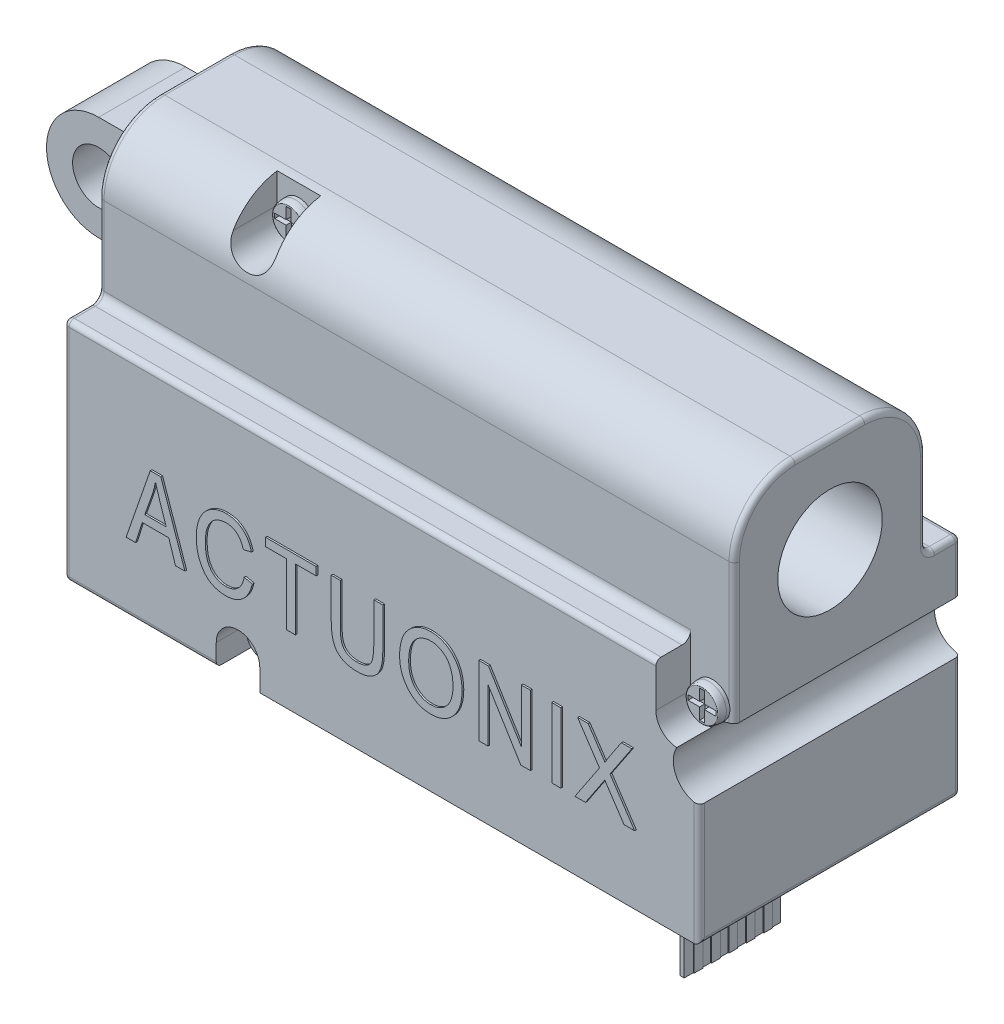
SolidWorks part; units mm, degrees
other "Body"
other "ConnectingWires"
other "Screw2"
other "Screw3"
other "Screw1"
ref_plane "Front Plane" through (0, 0, 0) normal (0, 0, 1) x (1, 0, 0)
ref_plane "Top Plane" through (0, 0, 0) normal (0, 1, 0) x (1, 0, 0)
ref_plane "Right Plane" through (0, 0, 0) normal (1, 0, 0) x (0, 0, -1)
sketch "Sketch1" plane through (0, 0, 0) normal (0, 0, 1) x (1, 0, 0)
  line L1 (-18.25, 10.75) -> (18.25, 10.75)
  line L2 (-18.25, 10.75) -> (-18.25, -10.75)
  line L3 (-18.25, -10.75) -> (18.25, -10.75)
  line L4 (18.25, 10.75) -> (18.25, -10.75)
  line L5 (-18.25, 10.75) -> (18.25, -10.75) construction
  line L6 (-18.25, -10.75) -> (18.25, 10.75) construction
  point P0 (0, 0)
  dimension "D1" = 36.5
  dimension "D2" = 21.5
extrude "Boss-Extrude1" add sketch "Sketch1" along normal mid plane 15
sketch "Sketch2" plane through (18.25, 0, 0) normal (1, 0, 0) x (0, 0, -1)
  line L0 (-7.5, -10.75) -> (-7.5, 2.25)
  line L1 (-7.5, -10.75) -> (-7.5, 10.75) construction
  line L2 (7.5, 2.25) -> (7.5, -10.75)
  line L3 (7.5, -10.75) -> (7.5, 10.75) construction
  line L4 (7.5, -10.75) -> (-7.5, -10.75)
  line L5 (0, -10.75) -> (0, 10.75) construction
  line L6 (-7.5, 10.75) -> (7.5, 10.75) construction
  line L7 (-5.5, 2.25) -> (-7.5, 2.25)
  line L8 (-5.5, 10.75) -> (5.5, 10.75)
  line L9 (-5.5, 10.75) -> (-5.5, 2.25)
  line L10 (-5.5, 2.25) -> (5.5, 2.25)
  line L11 (5.5, 10.75) -> (5.5, 2.25)
  line L12 (5.5, 2.25) -> (7.5, 2.25)
  dimension "D1" = 13
  dimension "D2" = 11
extrude "Cut-Extrude1" cut sketch "Sketch2" against normal through all contours L9 L2 L3 L7 | L11 L12 L1 L2
sketch "Sketch3" plane through (-18.25, 0, 0) normal (-1, 0, 0) x (0, 0, 1)
  line L0 (0, 10.75) -> (0, -10.75) construction
  line L1 (-2.5, 8.25) -> (2.5, 8.25)
  line L2 (-2.5, 8.25) -> (-2.5, 2.25)
  line L3 (-2.5, 2.25) -> (2.5, 2.25)
  line L4 (2.5, 8.25) -> (2.5, 2.25)
  line L5 (-2.5, 8.25) -> (2.5, 2.25) construction
  line L6 (-2.5, 2.25) -> (2.5, 8.25) construction
  line L7 (5.5, 10.75) -> (-5.5, 10.75) construction
  line L8 (7.5, -10.75) -> (-7.5, -10.75) construction
  point P0 (0, 5.25)
  point P12 (2.5, 5.25)
  dimension "D1" = 5
  dimension "D2" = 6
  dimension "D3" = 16
extrude "Boss-Extrude2" add sketch "Sketch3" along normal blind 6
sketch "Sketch4" plane through (0, 0, 2.5) normal (0, 0, 1) x (1, 0, 0)
  line L1 (-24.25, 2.25) -> (-24.25, 8.25) construction
  line L2 (-24.25, 8.25) -> (-18.25, 8.25) construction
  circle A0 centre (-21.25, 5.25) radius 1.5
  circle A1 centre (-21.25, 5.25) radius 3
  point P7 (-24.25, 5.25)
  point P9 (-21.25, 8.25)
  line M3 (-18.25, 8.25) -> (-24.25, 8.25)
  line M4 (-24.25, 8.25) -> (-24.25, 2.25)
  line M5 (-24.25, 2.25) -> (-18.25, 2.25)
  dimension "D1" = 3
extrude "Cut-Extrude2" cut sketch "Sketch4" against normal through all contours A1 M3 M4 | A1 M4 M5 | A0
sketch "Sketch5" plane through (0, 0, 7.5) normal (0, 0, 1) x (1, 0, 0)
  line L0 (18.25, -10.75) -> (18.25, 2.25) construction
  line L1 (-18.25, -10.75) -> (18.25, -10.75) construction
  circle A0 centre (18.25, -2.25) radius 1.5
  dimension "D1" = 3
  dimension "D2" = 8.5
extrude "Cut-Extrude3" cut sketch "Sketch5" against normal through all
sketch "Sketch6" plane through (18.25, 0, 0) normal (1, 0, 0) x (0, 0, -1)
  line L0 (0, 0) -> (0, 10.75) construction
  line L1 (-5.5, 10.75) -> (5.5, 10.75) construction
  line L2 (-7.5, -10.75) -> (7.5, -10.75) construction
  circle A0 centre (0, 5.25) radius 3
  point P10 (0, 8.25)
  dimension "D1" = 6
  dimension "D2" = 16
sketch "Sketch7" plane through (0, 0, 7.5) normal (0, 0, 1) x (1, 0, 0)
  line L0 (-18.25, -6.75) -> (18.25, -6.75) construction
  line L1 (-18.25, 2.25) -> (-18.25, -10.75) construction
  line L2 (18.25, -10.75) -> (18.25, -3.75) construction
  line L3 (-18.25, -10.75) -> (18.25, -10.75) construction
  text T0 "ACTUONIX" font "Arial Narrow" height 4
  dimension "D1" = 4
extrude "Lettering" add sketch "Sketch7" along normal blind 0.1
sketch "Sketch8" plane through (0, -10.75, 0) normal (0, -1, 0) x (1, 0, 0)
  line L0 (13.25, 3.5) -> (13.25, -2.75) construction
  line L1 (18.25, 7.5) -> (18.25, -7.5) construction
  line L3 (18.25, 3.5) -> (-18.25, 3.5) construction
  line L4 (-18.25, 7.5) -> (-18.25, -7.5) construction
  line L5 (-18.25, 7.5) -> (18.25, 7.5) construction
  line L6 (13.25, 7.5) -> (13.25, -7.5) construction
  line L7 (-18.25, -7.5) -> (18.25, -7.5) construction
  line L8 (14.5, 3.5) -> (14.5, -2.75)
  line L9 (12, 3.5) -> (12, -2.75)
  line L11 (13, 3.5) -> (13.5, 3.5)
  line L12 (13, 3.5) -> (13, -2.0239)
  line L13 (13, -2.0239) -> (13.5, -2.0239)
  line L14 (13.5, 3.5) -> (13.5, -2.0239)
  arc A1 (12, -2.75) -> (14.5, -2.75) centre (13.25, -2.75) ccw
  point P19 (13.25, -4)
  dimension "D1" = 4
  dimension "D2" = 5
  dimension "D3" = 7.5
  dimension "D4" = 2.5
  dimension "D5" = 0.5
  dimension "D6" = 5.5239
  dimension "D7" = 6.25
extrude "Cut-Extrude5" cut sketch "Sketch8" against normal blind 1 contours L14 L11 L12 L13
sketch "Sketch9" plane through (0, -10.75, 0) normal (0, -1, 0) x (1, 0, 0)
  line L0 (14.5, 3.5) -> (14.5, -2.75) construction
  line L1 (12, 3.5) -> (12, -2.75) construction
  line L2 (14.5, 3.5) -> (14.5, -2.75)
  line L3 (12, 3.5) -> (12, -2.75)
  line L4 (13.5, 3.5) -> (13, 3.5)
  line L5 (13.5, -2.0239) -> (13.5, 3.5)
  line L6 (13, -2.0239) -> (13.5, -2.0239)
  line L7 (13, 3.5) -> (13, -2.0239)
  line L8 (13.5, 3.5) -> (13, 3.5)
  line L9 (13.5, -2.0239) -> (13.5, 3.5)
  line L10 (13, -2.0239) -> (13.5, -2.0239)
  line L11 (13, 3.5) -> (13, -2.0239)
  line L12 (12, 3.5) -> (14.5, 3.5)
  arc A0 (12, -2.75) -> (14.5, -2.75) centre (13.25, -2.75) ccw construction
  arc A1 (12, -2.75) -> (14.5, -2.75) centre (13.25, -2.75) ccw
  line M9 (13.5, 3.5) -> (13.5, -2.0239)
  line M10 (13.5, -2.0239) -> (13, -2.0239)
  line M11 (13, -2.0239) -> (13, 3.5)
  dimension "D1" = 0
extrude "Boss-Extrude4" add sketch "Sketch9" along normal blind 0.1 contours L3 A1 L2 L12 M9 M10 M11
sketch "Sketch10" plane through (0, -9.75, 0) normal (0, -1, 0) x (1, 0, 0)
  line L0 (13, 3.5) -> (13.5, 3.5) construction
  line L1 (13.125, 3.5) -> (13.375, 3.5)
  line L2 (13.125, 3.5) -> (13.125, -2.0239)
  line L3 (13.125, -2.0239) -> (13.375, -2.0239)
  line L4 (13.375, 3.5) -> (13.375, -2.0239)
  line L5 (13, -2.0239) -> (13.5, -2.0239) construction
  line L6 (13.5, 3.5) -> (13.5, -2.0239) construction
  point P9 (13.25, 3.5)
  dimension "D1" = 0.25
  dimension "D2" = 0.25
extrude "Wires" add sketch "Sketch10" along normal blind 7 separate body
sketch "Sketch11" plane through (13.375, 0, 0) normal (1, 0, 0) x (0, 0, -1)
  line L0 (1.5221, -16.75) -> (1.5221, -9.75)
  line L1 (2.0239, -16.75) -> (-3.5, -16.75) construction
  line L2 (2.0239, -9.75) -> (-3.5, -9.75) construction
  line L3 (2.0239, -16.75) -> (2.0239, -9.75) construction
  line L4 (1.0221, -16.75) -> (1.0221, -9.75)
  line L5 (0.5221, -16.75) -> (0.5221, -9.75)
  line L6 (0.0221, -16.75) -> (0.0221, -9.75)
  line L7 (-0.4779, -16.75) -> (-0.4779, -9.75)
  line L8 (-0.9779, -16.75) -> (-0.9779, -9.75)
  line L9 (-1.4779, -16.75) -> (-1.4779, -9.75)
  line L10 (-1.9779, -16.75) -> (-1.9779, -9.75)
  line L11 (-2.4779, -16.75) -> (-2.4779, -9.75)
  line L12 (-2.9779, -16.75) -> (-2.9779, -9.75)
  line L13 (-3.5, -16.75) -> (-3.5, -9.75) construction
  line L14 (2.0239, -16.75) -> (-3.5, -16.75)
  line L15 (-3.5, -16.75) -> (-3.5, -9.75)
  line L16 (-3.5, -9.75) -> (2.0239, -9.75)
  line L17 (2.0239, -9.75) -> (2.0239, -16.75)
  line M11 (2.0239, -9.75) -> (-3.5, -9.75)
  line M13 (-3.5, -16.75) -> (2.0239, -16.75)
  dimension "D1" = 0.5018
  dimension "D3" = 0.5221
  dimension "D2" = 10
extrude "Boss-Extrude6" add sketch "Sketch11" along normal blind 0.05 contours L4 L0 M13 M11 | L6 L5 M13 M11 | L8 L7 M13 M11 | L10 L9 M13 M11 | L12 L11 M13 M11
ref_plane "Plane1" through (13.25, 0, 0) normal (1, 0, 0) x (0, 0, -1)
mirror "Mirror1" about plane through (13.25, 0, 0) normal (1, 0, 0) of "Boss-Extrude6"
sketch "Sketch12" plane through (0, 0, 7.5) normal (0, 0, 1) x (1, 0, 0)
  line L0 (17, 2.25) -> (17, -0.25) construction
  line L1 (-18.25, 2.25) -> (18.25, 2.25) construction
  line L2 (18.25, 2.25) -> (18.25, -0.25)
  line L3 (15.75, 2.25) -> (15.75, -0.25)
  line L4 (18.25, -0.75) -> (18.25, 2.25) construction
  line L5 (-18.25, 2.25) -> (18.25, 2.25) construction
  line L6 (18.25, -0.75) -> (18.25, 2.25)
  line L7 (-8.25, -10.75) -> (-8.25, -9.5) construction
  line L8 (-18.25, -10.75) -> (18.25, -10.75) construction
  line L9 (-9.5, -10.75) -> (-9.5, -9.5)
  line L10 (-7, -10.75) -> (-7, -9.5)
  line L11 (-18.25, 2.25) -> (-18.25, -10.75) construction
  arc A0 (18.25, 2.25) -> (15.75, 2.25) centre (17, 2.25) ccw
  arc A1 (15.75, -0.25) -> (18.25, -0.25) centre (17, -0.25) ccw
  arc A2 (18.25, -0.75) -> (18.25, -3.75) centre (18.25, -2.25) ccw construction
  arc A3 (18.25, -0.75) -> (16.9515, -1.4991) centre (18.25, -2.25) ccw
  arc A4 (-9.5, -10.75) -> (-7, -10.75) centre (-8.25, -10.75) ccw
  arc A5 (-7, -9.5) -> (-9.5, -9.5) centre (-8.25, -9.5) ccw
  point P4 (17, 1)
  point P20 (-8.25, -10.125)
  point P27 (-8.25, -8.25)
  dimension "D1" = 2.5
  dimension "D2" = 2.5
  dimension "D3" = 10
  dimension "D4" = 2.5
  dimension "D5" = 2.5
extrude "Cut-Extrude6" cut sketch "Sketch12" against normal up to surface (2 mm away)
sketch "Sketch13" plane through (0, 0, 5.5) normal (0, 0, 1) x (1, 0, 0)
  line L0 (-9.75, 10.75) -> (-9.75, 9) construction
  line L1 (-18.25, 10.75) -> (18.25, 10.75) construction
  line L2 (-8.5, 10.75) -> (-8.5, 9)
  line L3 (-11, 10.75) -> (-11, 9)
  line L4 (-18.25, 10.75) -> (-18.25, 2.25) construction
  arc A0 (-8.5, 10.75) -> (-11, 10.75) centre (-9.75, 10.75) ccw
  arc A1 (-11, 9) -> (-8.5, 9) centre (-9.75, 9) ccw
  point P4 (-9.75, 9.875)
  point P11 (-9.75, 7.75)
  dimension "D1" = 8.5
  dimension "D2" = 2.5
  dimension "D3" = 3
extrude "Cut-Extrude7" cut sketch "Sketch13" against normal blind 3
sketch "Sketch14" plane through (0, 0, 5.5) normal (0, 0, 1) x (1, 0, 0)
  line L0 (17, -0.25) -> (17, 10.75) construction
  line L1 (-8.5, 10.75) -> (18.25, 10.75) construction
  circle A0 centre (-8.25, -9.5) radius 1
  circle A1 centre (17, -0.0849) radius 1
  arc A2 (18.25, -0.75) -> (16.9515, -1.4991) centre (18.25, -2.25) ccw construction
  dimension "D1" = 2
extrude "Boss-Extrude7" add sketch "Sketch14" along normal blind 0.6 separate body
sketch "Sketch15" plane through (0, 0, 6.1) normal (0, 0, 1) x (1, 0, 0)
  line L1 (-9.05, -9.3625) -> (-7.45, -9.3625)
  line L3 (16.2, 0.0526) -> (17.8, 0.0526)
  line L4 (-9.05, -9.3625) -> (-9.05, -9.6375)
  line L5 (-9.05, -9.6375) -> (-7.45, -9.6375)
  line L6 (-7.45, -9.3625) -> (-7.45, -9.6375)
  line L7 (-9.05, -9.3625) -> (-7.45, -9.6375) construction
  line L8 (-9.05, -9.6375) -> (-7.45, -9.3625) construction
  line L9 (-8.3875, -8.7) -> (-8.1125, -8.7)
  line L10 (-8.3875, -8.7) -> (-8.3875, -10.3)
  line L11 (-8.3875, -10.3) -> (-8.1125, -10.3)
  line L12 (-8.1125, -8.7) -> (-8.1125, -10.3)
  line L13 (-8.3875, -8.7) -> (-8.1125, -10.3) construction
  line L14 (-8.3875, -10.3) -> (-8.1125, -8.7) construction
  line L15 (16.2, 0.0526) -> (16.2, -0.2224)
  line L16 (16.2, -0.2224) -> (17.8, -0.2224)
  line L17 (17.8, 0.0526) -> (17.8, -0.2224)
  line L18 (16.2, 0.0526) -> (17.8, -0.2224) construction
  line L19 (16.2, -0.2224) -> (17.8, 0.0526) construction
  line L20 (16.8625, -0.8849) -> (17.1375, -0.8849)
  line L21 (16.8625, -0.8849) -> (16.8625, 0.7151)
  line L22 (16.8625, 0.7151) -> (17.1375, 0.7151)
  line L23 (17.1375, -0.8849) -> (17.1375, 0.7151)
  line L24 (16.8625, -0.8849) -> (17.1375, 0.7151) construction
  line L25 (16.8625, 0.7151) -> (17.1375, -0.8849) construction
  point P0 (-8.25, -9.5)
  point P1 (-8.25, -9.5)
  point P7 (17, -0.0849)
  point P8 (17, -0.0849)
  point P14 (-8.25, -9.5)
  point P15 (17, -0.0849)
  dimension "D1" = 1.6
  dimension "D2" = 0.275
  dimension "D3" = 0.275
  dimension "D4" = 1.6
extrude "Cut-Extrude8" cut sketch "Sketch15" against normal blind 0.3 contours L16 L21 L3 L15 | L16 L23 L3 L21 | L3 L23 L22 L21 | L23 L16 L17 L3 | L20 L23 L16 L21 | L12 L5 L10 L11 | L10 L1 L4 L5 | L12 L9 L10 L1 | L1 L12 L5 L6 | L12 L1 L10 L5
sketch "Sketch16" plane through (0, 0, 2.5) normal (0, 0, 1) x (1, 0, 0)
  circle A0 centre (-9.75, 9) radius 1
  dimension "D1" = 2
extrude "Boss-Extrude8" add sketch "Sketch16" along normal blind 0.6 separate body
sketch "Sketch17" plane through (0, 0, 3.1) normal (0, 0, 1) x (1, 0, 0)
  line L1 (-9.8875, 9.8) -> (-9.6125, 9.8)
  line L2 (-9.8875, 9.8) -> (-9.8875, 8.2)
  line L3 (-9.8875, 8.2) -> (-9.6125, 8.2)
  line L4 (-9.6125, 9.8) -> (-9.6125, 8.2)
  line L5 (-9.8875, 9.8) -> (-9.6125, 8.2) construction
  line L6 (-9.8875, 8.2) -> (-9.6125, 9.8) construction
  line L7 (-10.55, 9.1375) -> (-8.95, 9.1375)
  line L8 (-10.55, 9.1375) -> (-10.55, 8.8625)
  line L9 (-10.55, 8.8625) -> (-8.95, 8.8625)
  line L10 (-8.95, 9.1375) -> (-8.95, 8.8625)
  line L11 (-10.55, 9.1375) -> (-8.95, 8.8625) construction
  line L12 (-10.55, 8.8625) -> (-8.95, 9.1375) construction
  point P0 (-9.75, 9)
  point P6 (-9.75, 9)
  dimension "D1" = 0.275
  dimension "D2" = 1.6
extrude "Cut-Extrude9" cut sketch "Sketch17" against normal blind 0.3 contours L9 L2 L3 L4 | L10 L7 L4 L9 | L2 L9 L4 L7 | L8 L9 L2 L7 | L2 L7 L4 L1
fillet "Fillet6" radius 0.1 1 edges at (-8.75, 9, 3.1)
fillet "Fillet7" radius 0.1 1 edges at (-7.25, -9.5, 6.1)
fillet "Fillet8" radius 0.1 1 edges at (18, -0.0849, 6.1)
fillet "Fillet1" radius 3.5 3 edges at (0, 10.75, -5.5) (4.875, 10.75, 5.5) (-14.625, 10.75, 5.5)
fillet "Fillet2" radius 1 2 edges at (-18.25, 2.25, 0) (-18.25, 8.25, 0)
fillet "Fillet3" radius 0.5 2 edges at (-18.25, 5.25, 2.5) (-18.25, 5.25, -2.5)
fillet "Fillet4" radius 0.5 2 edges at (-1.25, 2.25, 5.5) (0, 2.25, -5.5)
fillet "Fillet5" radius 0.3 26 edges at (-18.25, -4.25, -7.5) (-18.25, -4.25, 7.5) (-1.25, 2.25, 7.5) (0, 2.25, -7.5) (18.25, -7.25, 7.5) (18.25, 5, -5.5) (-18.25, 5, -5.5) (18.25, 3.25, 5.5) (18.25, 10.75, 0) (18.25, 9.7249, 4.4749) (18.25, 9.7249, -4.4749) (-18.25, 10.75, 0) (-18.25, 5, 5.5) (-18.25, 9.7249, 4.4749) (-18.25, 9.7249, -4.4749) (0, -10.75, -7.5) (-18.25, 2.25, 6.75) (18.25, 2.25, -6.75) (-18.25, 2.25, -6.75) (-18.25, 2.3964, 5.6464) (18.25, 2.3964, -5.6464) (-18.25, 2.3964, -5.6464) (18.25, -7.25, -7.5) (18.25, -10.75, 0) (-18.25, -10.75, 0) (18.25, 0.75, -7.5)
extrude "Cut-Extrude4" cut sketch "Sketch6" against normal blind 25
